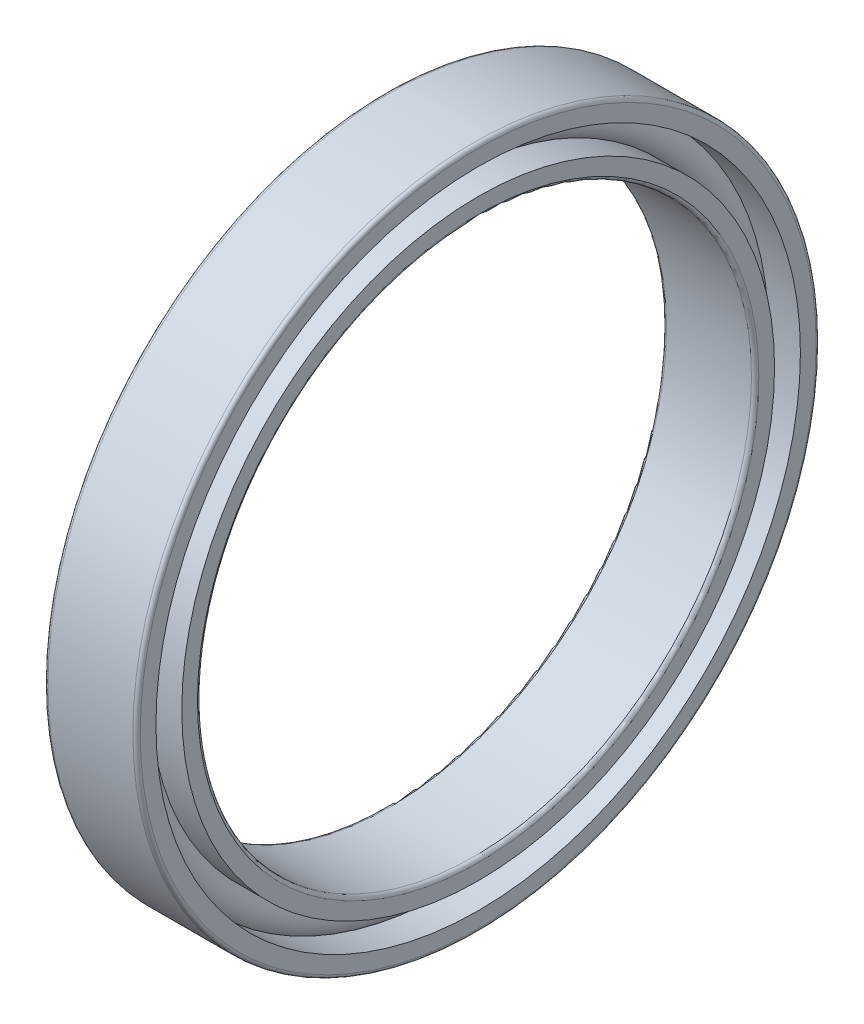
SolidWorks part; units mm, degrees
material "Alloy Steel"
ref_plane "Plane1" through (0, 0, 0) normal (0, 0, 1) x (1, 0, 0)
ref_plane "Plane2" through (0, 0, 0) normal (0, 1, 0) x (1, 0, 0)
ref_plane "Plane3" through (0, 0, 0) normal (1, 0, 0) x (0, 0, -1)
other "Configuration Table"
sketch "Clipboard" plane through (0, 0, 0) normal (0, 0, 1) x (1, 0, 0)
  line L0 (-10, 0) -> (10, 0) construction
  line L1 (0, 0) -> (22.3471, -0.7804)
  line L2 (0, 0) -> (16.7398, 0.5846)
  line L3 (0, 0) -> (22.3471, -0.7804)
  line L4 (0, 0) -> (-22.3573, -0.3902)
  dimension "BallCLRad" = 16.75
  dimension "Count" = 2
sketch "CagSpiSke" plane through (0, 0, 0) normal (0, 0, 1) x (1, 0, 0)
  line L0 (0.105, 16.575) -> (0.105, 16.925)
  line L1 (0.105, 16.925) -> (-0.105, 16.925)
  line L2 (-0.105, 16.925) -> (-0.105, 16.575)
  line L3 (-0.105, 16.575) -> (0.105, 16.575)
  line L4 (-20.6375, 0) -> (20.6375, 0) construction
  line L5 (0, 0) -> (0, 23.7692) construction
  dimension "OD" = 33.85
  dimension "ID" = 33.15
revolve "CageSpine" add sketch "CagSpiSke" angle 0.001 about L4 reverse direction yes
ref_axis "Axis1" through (-50, 0, 0) along (1, 0, 0)
sketch "CagBalSke" plane through (0, 0, 0) normal (0, 0, 1) x (1, 0, 0)
  line L0 (-1.155, 16.75) -> (1.155, 16.75)
  line L1 (-1.905, 16.75) -> (1.905, 16.75) construction
  line L2 (-10, 0) -> (10, 0) construction
  line L3 (0, 0) -> (0, 24) construction
  arc A0 (1.155, 16.75) -> (-1.155, 16.75) centre (0, 16.75) cw
  dimension "BallCLRad" = 16.75
revolve "CageBall" [suppressed] add sketch "CagBalSke" angle 360 about L1 reverse direction yes
pattern_circular "CageBalls" [suppressed] count 2 every 180 about axis through (-50, 0, 0) along (1, 0, 0)
sketch "CagTrmODSke" plane through (0, 0, 0) normal (0, 0, 1) x (1, 0, 0)
  line L0 (1.156, 16.925) -> (1.156, 17.906)
  line L1 (1.156, 17.906) -> (-1.156, 17.906)
  line L2 (-1.156, 17.906) -> (-1.156, 16.925)
  line L3 (-1.156, 16.925) -> (1.156, 16.925)
  line L4 (-20.6375, 0) -> (20.6375, 0) construction
  line L5 (0, 0) -> (0, 25) construction
  dimension "Width" = 2.312
  dimension "ID" = 33.85
  dimension "OD" = 35.812
revolve "CageTrimOD" [suppressed] cut sketch "CagTrmODSke" angle 360 about L4 reverse direction yes
sketch "CagTrmIDSke" plane through (0, 0, 0) normal (0, 0, 1) x (1, 0, 0)
  line L0 (1.156, 15.596) -> (1.156, 16.575)
  line L1 (1.156, 16.575) -> (-1.156, 16.575)
  line L2 (-1.156, 16.575) -> (-1.156, 15.596)
  line L3 (-1.156, 15.596) -> (1.156, 15.596)
  line L4 (-20.6375, 0) -> (20.6375, 0) construction
  line L5 (0, 0) -> (0, 25) construction
  dimension "Width" = 2.312
  dimension "ID" = 31.192
  dimension "OD" = 33.15
revolve "CageTrimID" [suppressed] cut sketch "CagTrmIDSke" angle 360 about L4 reverse direction yes
sketch "BalSimSke" plane through (0, 0, 0) normal (0, 0, 1) x (1, 0, 0)
  line L0 (-10, 0) -> (10, 0) construction
  line L1 (-10, 16.75) -> (10, 16.75) construction
  line L2 (0, 0) -> (0, 23) construction
  circle A0 centre (0, 16.75) radius 1.05
  dimension "BallCLRad" = 16.75
revolve "BallsSimplified" add sketch "BalSimSke" angle 360 about L0
sketch "BalDetSke" plane through (0, 0, 0) normal (0, 0, 1) x (1, 0, 0)
  line L0 (-1.05, 16.75) -> (1.05, 16.75)
  line L1 (-1.905, 16.75) -> (1.905, 16.75) construction
  line L2 (0, 0) -> (0, 25) construction
  arc A0 (1.05, 16.75) -> (-1.05, 16.75) centre (0, 16.75) cw
  dimension "BallCLRad" = 16.75
revolve "BallDetailed" [suppressed] add sketch "BalDetSke" angle 360 about L1 reverse direction yes
sketch "InnRacSke" plane through (0, 0, 0) normal (0, 0, 1) x (1, 0, 0)
  line L0 (-0.7487, 16.05) -> (-2.5, 16.05)
  line L1 (-2.5, 16.05) -> (-2.5, 15.2)
  line L2 (-2.3, 15) -> (2.3, 15)
  line L3 (2.5, 15.2) -> (2.5, 16.05)
  line L4 (2.5, 16.05) -> (0.7487, 16.05)
  line L5 (-20.6375, 0) -> (20.6375, 0) construction
  line L6 (0, 0) -> (0, 30) construction
  arc A0 (-2.5, 15.2) -> (-2.3, 15) centre (-2.3, 15.2) ccw
  arc A1 (2.3, 15) -> (2.5, 15.2) centre (2.3, 15.2) ccw
  arc A2 (0.7487, 16.05) -> (-0.7487, 16.05) centre (0, 16.75) cw
  dimension "BallCLRad" = 16.75
  dimension "Fillet_radius" = 0.2
  dimension "Ball_diameter" = 2.05
  dimension "ID" = 30
  dimension "OD" = 32.1
  dimension "Width" = 5
revolve "InnerRace" add sketch "InnRacSke" angle 360 about L5 reverse direction yes
sketch "OutRacSke" plane through (0, 0, 0) normal (0, 0, 1) x (1, 0, 0)
  line L0 (-0.7487, 17.45) -> (-2.5, 17.45)
  line L1 (-2.5, 17.45) -> (-2.5, 18.3)
  line L2 (-2.3, 18.5) -> (2.3, 18.5)
  line L3 (2.5, 18.3) -> (2.5, 17.45)
  line L4 (2.5, 17.45) -> (0.7487, 17.45)
  line L5 (-20.6375, 0) -> (20.6375, 0) construction
  line L6 (0, 0) -> (0, 30) construction
  arc A0 (-2.5, 18.3) -> (-2.3, 18.5) centre (-2.3, 18.3) cw
  arc A1 (2.3, 18.5) -> (2.5, 18.3) centre (2.3, 18.3) cw
  arc A2 (0.7487, 17.45) -> (-0.7487, 17.45) centre (0, 16.75) ccw
  dimension "BallCLRad" = 16.75
  dimension "Fillet_radius" = 0.2
  dimension "Ball_diameter" = 2.05
  dimension "Width" = 5
revolve "OuterRace" add sketch "OutRacSke" angle 360 about L5 reverse direction yes
pattern_circular "BallsDetailed" [suppressed] count 2 every 180 about axis through (-50, 0, 0) along (1, 0, 0)
equation "\"BallCLRad@Clipboard\" = ( \"OD@OutRacSke\" + \"ID@InnRacSke\" ) / 4"
equation "\"BallCLRad@BalSimSke\" = \"BallCLRad@Clipboard\""
equation "\"BallCLRad@BalDetSke\" = \"BallCLRad@Clipboard\""
equation "\"BallCLRad@InnRacSke\" = \"BallCLRad@Clipboard\""
equation "\"BallCLRad@OutRacSke\" = \"BallCLRad@Clipboard\""
equation "\"Ball_diameter@InnRacSke\" = \"Ball_diameter@BalDetSke\" - 0.05"
equation "\"Ball_diameter@OutRacSke\" = \"Ball_diameter@BalDetSke\" - 0.05"
equation "\"Ball_diameter@BalSimSke\" = \"Ball_diameter@BalDetSke\""
equation "\"Width@OutRacSke\" = \"Width@InnRacSke\""
equation "\"Fillet_radius@OutRacSke\" = \"Fillet_radius@InnRacSke\""
equation "\"Max_count@Clipboard\" = int( 3.14159265 / atn(( \"Ball_diameter@BalDetSke\" / 2) / sqr( \"BallCLRad@Clipboard\"  *  \"BallCLRad@Clipboard\" - ( \"Ball_diameter@BalDetSke\" / 2) *  ( \"Ball_diameter@BalDetSke\" / 2))))"
equation "\"Max_count@Clipboard\" = ((sgn( \"Max_count@Clipboard\" - \"Count@Clipboard\" )-1)*( \"Max_count@Clipboard\" - \"Count@Clipboard\" ))/-2+ \"Count@Clipboard\""
equation "\"Count@BallsDetailed\" = int( \"Show_count@Clipboard\" ) "
equation "\"Count@BallsDetailed\" = ((sgn( \"Count@BallsDetailed\" - \"Max_count@Clipboard\" )-1)*( \"Count@BallsDetailed\" - \"Max_count@Clipboard\" ))/-2+ \"Max_count@Clipboard\""
equation "\"Count@BallsDetailed\" = ((sgn( \"Count@BallsDetailed\" - \"Min_count@Clipboard\" )+1)*( \"Count@BallsDetailed\" - \"Min_count@Clipboard\"))/2 +\"Min_count@Clipboard\""
equation "\"Angle@BallsDetailed\" = 360.0 / \"Max_count@Clipboard\""
equation "\"BallCLRad@CagBalSke\" = \"BallCLRad@Clipboard\""
equation "\"Count@CageBalls\" = \"Count@BallsDetailed\""
equation "\"Angle@CageBalls\" = \"Angle@BallsDetailed\""
equation "\"Angle@CageSpine\" =  \"Angle@CageBalls\" * ( \"Count@CageBalls\" -1 + int( \"Count@CageBalls\" / \"Max_count@Clipboard\" ) )  + 0.001 -  int( \"Count@CageBalls\" / \"Max_count@Clipboard\" ) * 0.001"
equation "\"Angle@CageSpine\" =  \"Angle@CageSpine\" * int( \"Min_count@Clipboard\" / 2) + int(1 / \"Min_count@Clipboard\")  * 0.001"
equation "\"CageWallOD@CagBalSke\" =  \"Ball_diameter@BalDetSke\" * 1.1"
equation "\"Thickness@CagSpiSke\" =  \"Ball_diameter@BalDetSke\" * 0.1"
equation "\"OD@CagTrmODSke\" = \"BallCLRad@Clipboard\" * 2 + \"CageWallOD@CagBalSke\" + 0.002"
equation "\"ID@CagTrmODSke\" = \"BallCLRad@Clipboard\" * 2 + \"Ball_diameter@BalDetSke\" / 6"
equation "\"OD@CagTrmIDSke\" = \"BallCLRad@Clipboard\" * 2 - \"Ball_diameter@BalDetSke\" / 6"
equation "\"ID@CagTrmIDSke\" = \"BallCLRad@Clipboard\" * 2 - \"CageWallOD@CagBalSke\" + 0.002"
equation "\"OD@CagSpiSke\" = \"ID@CagTrmODSke\""
equation "\"ID@CagSpiSke\" = \"OD@CagTrmIDSke\""
equation "\"Width@CagTrmODSke\" = \"CageWallOD@CagBalSke\" + 0.002"
equation "\"Width@CagTrmIDSke\" = \"CageWallOD@CagBalSke\" + 0.002"
